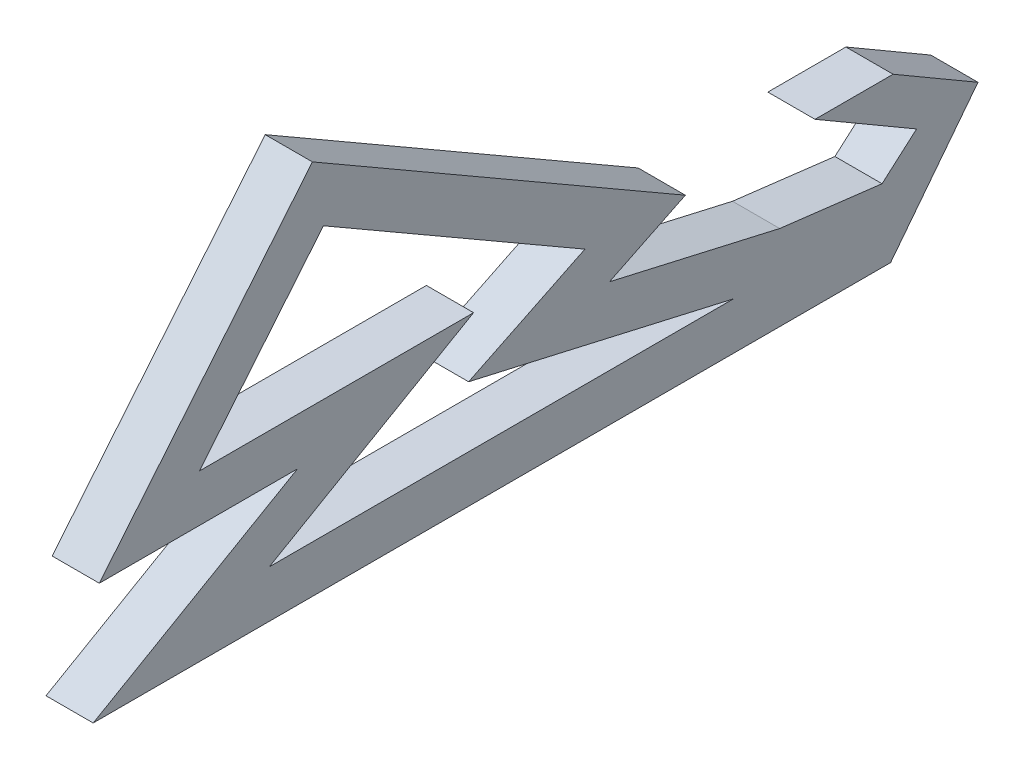
SolidWorks part; units mm, degrees
ref_plane "Front Plane" through (0, 0, 0) normal (0, 0, 1) x (1, 0, 0)
ref_plane "Top Plane" through (0, 0, 0) normal (0, 1, 0) x (1, 0, 0)
ref_plane "Right Plane" through (0, 0, 0) normal (1, 0, 0) x (0, 0, -1)
sketch "Sketch1" plane through (0, 0, 0) normal (1, 0, 0) x (0, 0, -1)
  line L0 (-84.5, 0) -> (84.5, 0)
  line L1 (-84.5, 0) -> (-41.1987, 25)
  line L2 (-41.1987, 25) -> (-83.1987, 25)
  line L4 (-38.0409, 79.7571) -> (41.0019, 34.1218)
  line L5 (41.0019, 34.1218) -> (24.9115, 26.2739)
  line L11 (103.0227, 23.8373) -> (84.5, 0)
  line L12 (19.7143, 34.8652) -> (-4.9305, 22.8451)
  line L13 (51.1954, 10) -> (-4.9305, 22.8451)
  line L15 (51.1954, 10) -> (51.1954, 10)
  line L16 (51.1954, 10) -> (51.1954, 10)
  line L17 (51.1954, 10) -> (51.1954, 10)
  line L18 (51.1954, 10) -> (51.1954, 10)
  line L19 (51.1954, 10) -> (51.1954, 10)
  line L29 (85.0303, 34.3106) -> (103.0227, 23.8373)
  line L30 (85.0303, 34.3106) -> (68.4811, 34.3106)
  line L31 (68.4811, 34.3106) -> (90.0065, 21.7808)
  line L32 (90.0065, 21.7808) -> (82.6905, 15.3854)
  line L33 (-83.1987, 25) -> (-38.0409, 79.7571)
  line L34 (60.9997, 18.0147) -> (82.6905, 15.3854)
  line L38 (60.9997, 18.0147) -> (24.9115, 26.2739)
  line L39 (51.1954, 10) -> (51.1954, 10)
  line L40 (-47.1795, 10) -> (51.1954, 10)
  line L41 (-47.1795, 10) -> (-3.8782, 35)
  line L42 (-3.8782, 35) -> (-61.9898, 35)
  line L43 (-61.9898, 35) -> (-35.711, 66.865)
  line L44 (-35.711, 66.865) -> (19.7143, 34.8652)
  point P4 (0, 0)
  dimension "D1" = 169
  dimension "D2" = 50
  dimension "D3" = 30
  dimension "D4" = 42
  dimension "D5" = 10
  dimension "D10" = 56
extrude "Boss-Extrude1" add sketch "Sketch1" along normal blind 10
